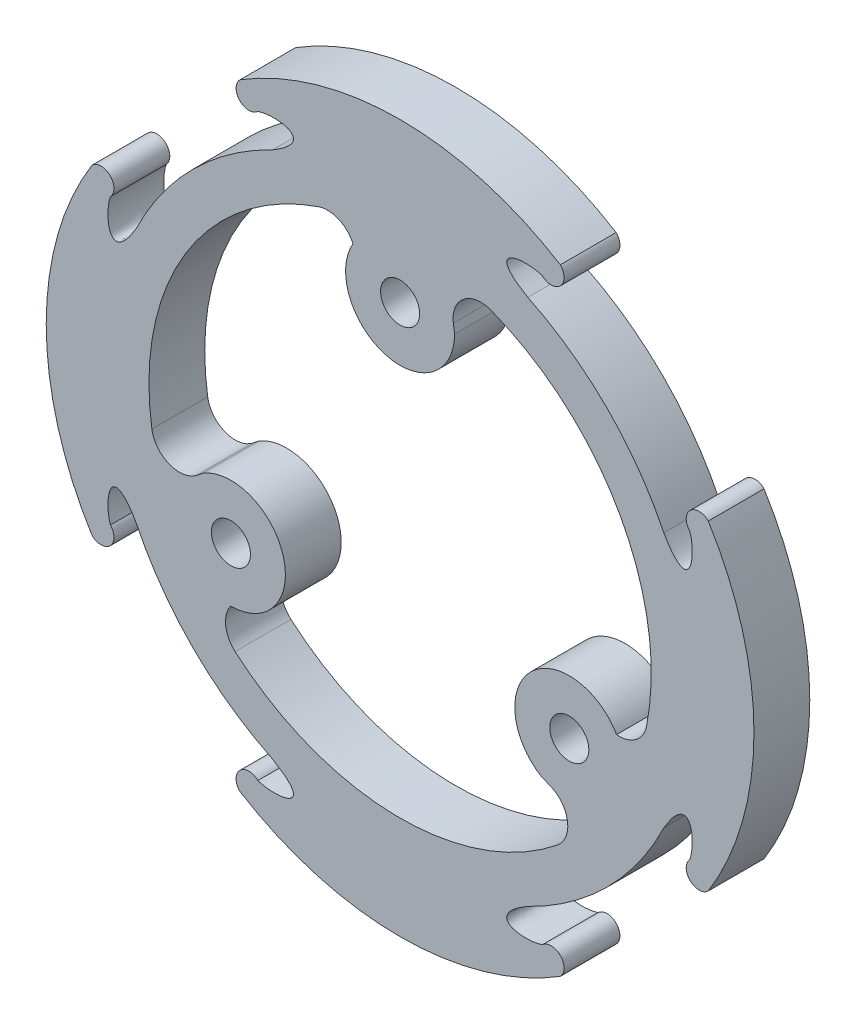
SolidWorks part; units mm, degrees
ref_plane "Front Plane" through (0, 0, 0) normal (0, 0, 1) x (1, 0, 0)
ref_plane "Top Plane" through (0, 0, 0) normal (0, 1, 0) x (1, 0, 0)
ref_plane "Right Plane" through (0, 0, 0) normal (1, 0, 0) x (0, 0, -1)
sketch "Sketch1" plane through (0, 0, 0) normal (0, 0, 1) x (1, 0, 0)
  line L0 (0, 0) -> (0, 17.78) construction
  line L1 (0, 17.78) -> (0, 20.32) construction
  line L2 (-4.2862, 20.275) -> (-4.2862, 22.4546)
  line L3 (4.9595, 17.78) -> (4.2862, 22.4546)
  line L8 (12.9182, -13.1851) -> (17.3031, -14.9393)
  line L9 (19.7017, -6.4255) -> (21.5894, -7.5153)
  line L12 (-17.8777, -4.5949) -> (-21.5894, -7.5153)
  line L13 (-15.4155, -13.8495) -> (-17.3031, -14.9393)
  line L14 (0, -55) -> (0, 55) construction
  circle A0 centre (0, 17.78) radius 1.778
  arc A1 (23.0969, 13.335) -> (11.6299, 24.0007) centre (0, 0) ccw
  arc A2 (-4.2862, 22.4546) -> (-19.7973, 11.43) centre (0, 0) ccw
  arc A3 (-4.2862, 20.275) -> (4.9595, 17.78) centre (0, 17.78) ccw
  arc A5 (19.7973, 11.43) -> (4.2862, 22.4546) centre (0, 0) ccw
  arc A6 (11.6299, -24.0007) -> (24.0007, -11.6299) centre (0, 0) ccw
  arc A7 (0, -22.86) -> (17.3031, -14.9393) centre (0, 0) ccw
  arc A8 (19.7017, -6.4255) -> (12.9182, -13.1851) centre (15.3979, -8.89) ccw
  arc A9 (21.5894, -7.5153) -> (19.7973, 11.43) centre (0, 0) ccw
  circle A10 centre (15.3979, -8.89) radius 1.778
  arc A11 (-23.0969, 13.335) -> (-24.0007, 11.6299) centre (0, 0) ccw
  arc A12 (-19.7973, 11.43) -> (-21.5894, -7.5153) centre (0, 0) ccw
  arc A13 (-15.4155, -13.8495) -> (-17.8777, -4.5949) centre (-15.3979, -8.89) ccw
  arc A14 (-17.3031, -14.9393) -> (0, -22.86) centre (0, 0) ccw
  circle A15 centre (-15.3979, -8.89) radius 1.778
  arc A16 (-14.5798, 28.0468) -> (14.5798, 28.0468) centre (0, 4.5835) cw
  arc A17 (12.9427, 26.3676) -> (14.5798, 28.0468) centre (13.7547, 27.2136) ccw
  arc A18 (-12.9427, 26.3676) -> (-14.5798, 28.0468) centre (-13.7547, 27.2136) cw
  arc A19 (-11.6299, 24.0007) -> (-23.0969, 13.335) centre (0, 0) ccw
  arc A20 (28.0468, 14.5798) -> (28.0468, -14.5798) centre (4.5835, 0) cw
  arc A21 (26.3676, -12.9427) -> (28.0468, -14.5798) centre (27.2136, -13.7547) ccw
  arc A22 (26.3676, 12.9427) -> (28.0468, 14.5798) centre (27.2136, 13.7547) cw
  arc A23 (14.5798, -28.0468) -> (-14.5798, -28.0468) centre (0, -4.5835) cw
  arc A24 (-12.9427, -26.3676) -> (-14.5798, -28.0468) centre (-13.7547, -27.2136) ccw
  arc A25 (12.9427, -26.3676) -> (14.5798, -28.0468) centre (13.7547, -27.2136) cw
  arc A26 (-28.0468, -14.5798) -> (-28.0468, 14.5798) centre (-4.5835, 0) cw
  arc A27 (-26.3676, 12.9427) -> (-28.0468, 14.5798) centre (-27.2136, 13.7547) ccw
  arc A28 (-26.3676, -12.9427) -> (-28.0468, -14.5798) centre (-27.2136, -13.7547) cw
  arc A29 (24.0007, 11.6299) -> (23.0969, 13.335) centre (0, 0) ccw
  arc A30 (-24.0007, -11.6299) -> (-11.6299, -24.0007) centre (0, 0) ccw
  spline S0 degree 3 poles (12.9427, 26.3676) (12.4899, 26.5244) (10.2146, 26.8236) (8.515, 25.8051) (11.6299, 24.0007) knots 0.119188 0.119188 0.119188 0.119188 0.354139 1 1 1 1
  spline S1 degree 3 poles (-12.9427, 26.3676) (-12.4899, 26.5244) (-10.2146, 26.8236) (-8.515, 25.8051) (-11.6299, 24.0007) knots 0.119188 0.119188 0.119188 0.119188 0.354139 1 1 1 1
  spline S2 degree 3 poles (26.3676, -12.9427) (26.5244, -12.4899) (26.8236, -10.2146) (25.8051, -8.515) (24.0007, -11.6299) knots 0.119188 0.119188 0.119188 0.119188 0.354139 1 1 1 1
  spline S3 degree 3 poles (26.3676, 12.9427) (26.5244, 12.4899) (26.8236, 10.2146) (25.8051, 8.515) (24.0007, 11.6299) knots 0.119188 0.119188 0.119188 0.119188 0.354139 1 1 1 1
  spline S4 degree 3 poles (-12.9427, -26.3676) (-12.4899, -26.5244) (-10.2146, -26.8236) (-8.515, -25.8051) (-11.6299, -24.0007) knots 0.119188 0.119188 0.119188 0.119188 0.354139 1 1 1 1
  spline S5 degree 3 poles (12.9427, -26.3676) (12.4899, -26.5244) (10.2146, -26.8236) (8.515, -25.8051) (11.6299, -24.0007) knots 0.119188 0.119188 0.119188 0.119188 0.354139 1 1 1 1
  spline S6 degree 3 poles (-26.3676, 12.9427) (-26.5244, 12.4899) (-26.8236, 10.2146) (-25.8051, 8.515) (-24.0007, 11.6299) knots 0.119188 0.119188 0.119188 0.119188 0.354139 1 1 1 1
  spline S7 degree 3 poles (-26.3676, -12.9427) (-26.5244, -12.4899) (-26.8236, -10.2146) (-25.8051, -8.515) (-24.0007, -11.6299) knots 0.119188 0.119188 0.119188 0.119188 0.354139 1 1 1 1
  point P6 (0, 19.05)
  point P37 (0, 0)
  point P86 (0, 0)
  dimension "D1" = 17.78
  dimension "D2" = 3.556
  dimension "D3" = 53.34
  dimension "D4" = 45.72
  dimension "D5" = 4
  dimension "D7" = 3
extrude "Boss-Extrude1" add sketch "Sketch1" along normal mid plane 5.08
fillet "Fillet1" radius 2.54 6 edges at (21.5894, -7.5153, 0) (17.3031, -14.9393, 0) (-17.3031, -14.9393, 0) (-21.5894, -7.5153, 0) (-4.2863, 22.4546, 0) (4.2862, 22.4546, 0)
